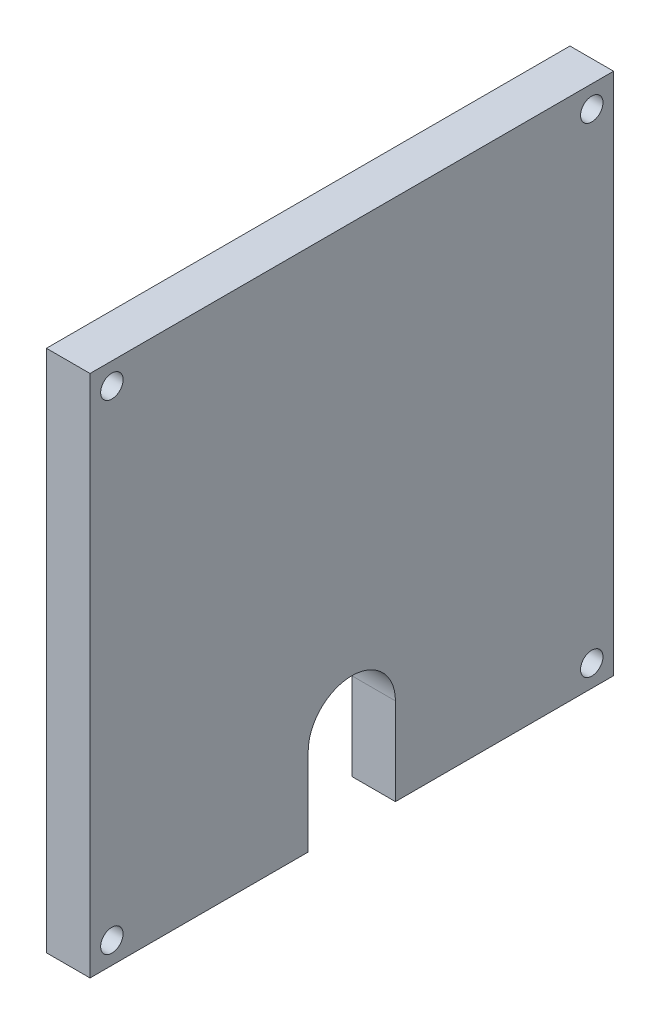
SolidWorks part; units mm, degrees
ref_plane "Front Plane" through (0, 0, 0) normal (0, 0, 1) x (1, 0, 0)
ref_plane "Top Plane" through (0, 0, 0) normal (0, 1, 0) x (1, 0, 0)
ref_plane "Right Plane" through (0, 0, 0) normal (1, 0, 0) x (0, 0, -1)
sketch "Sketch1" plane through (0, 0, 0) normal (1, 0, 0) x (0, 0, -1)
  line L1 (-38.1, -38.1) -> (38.1, -38.1)
  line L2 (-38.1, -38.1) -> (-38.1, 38.1)
  line L3 (-38.1, 38.1) -> (38.1, 38.1)
  line L4 (38.1, -38.1) -> (38.1, 38.1)
  line L5 (-38.1, -38.1) -> (38.1, 38.1) construction
  line L6 (-38.1, 38.1) -> (38.1, -38.1) construction
  point P0 (0, 0)
  dimension "D1" = 76.2
  dimension "D2" = 76.2
extrude "Boss-Extrude1" add sketch "Sketch1" along normal blind 6.35
hole_wizard "#4 Clearance Hole1" positions "Sketch2" profile "Sketch3" hole size "#4" standard "ANSI Inch" end condition through all
sketch "Sketch2" plane through (6.35, 0, 0) normal (1, 0, 0) x (0, 0, -1)
  line L0 (-38.1, 38.1) -> (-38.1, -38.1) construction
  line L1 (38.1, 38.1) -> (-38.1, 38.1) construction
  point P0 (-34.925, 34.925)
  dimension "D1" = 3.175
  dimension "D2" = 3.175
sketch "Sketch3" plane through (6.35, 34.925, 34.925) normal (0, 1, 0) x (0, 0, -1)
  line L0 (0, 0) -> (0, 6.35)
  line L1 (0, 6.35) -> (1.6319, 6.35)
  line L2 (1.6319, 6.35) -> (1.6319, 0)
  line L5 (1.6319, 0) -> (0, 0)
  line L11 (0, -6.35) -> (0, 107.95) construction
  dimension "Thru Hole Dia." = 3.2639
  dimension "Thru Hole Depth" = 6.35
mirror "Mirror1" about plane through (0, 0, 0) normal (0, 0, 1) of "#4 Clearance Hole1"
mirror "Mirror2" about plane through (0, 0, 0) normal (0, 1, 0) of "Mirror1"
hole_wizard "1/2 (0.5) Diameter Slot1" positions "Sketch6" profile "Sketch7" size "1/2" standard "ANSI Inch" slot yes end condition through all
sketch "Sketch6" plane through (6.35, 0, 0) normal (1, 0, 0) x (0, 0, -1)
  line L0 (0, -57.15) -> (0, -19.05) construction
  line L2 (-38.1, -38.1) -> (38.1, -38.1) construction
  line L3 (-38.1, 38.1) -> (-38.1, -38.1) construction
  point P0 (0, -38.1)
  dimension "D1" = 38.1
  dimension "D2" = 19.05
  dimension "D3" = 19.05
  dimension "D4" = 38.1
sketch "Sketch7" plane through (6.35, -38.1, 0) normal (0, 1, 0) x (0, 0, -1)
  line L0 (0, 0) -> (0, 6.35)
  line L1 (0, 6.35) -> (6.35, 6.35)
  line L2 (6.35, 6.35) -> (6.35, 0)
  line L5 (6.35, 0) -> (0, 0)
  line L11 (0, -6.35) -> (0, 107.95) construction
  dimension "Thru Hole Dia." = 12.7
  dimension "Thru Hole Depth" = 6.35
